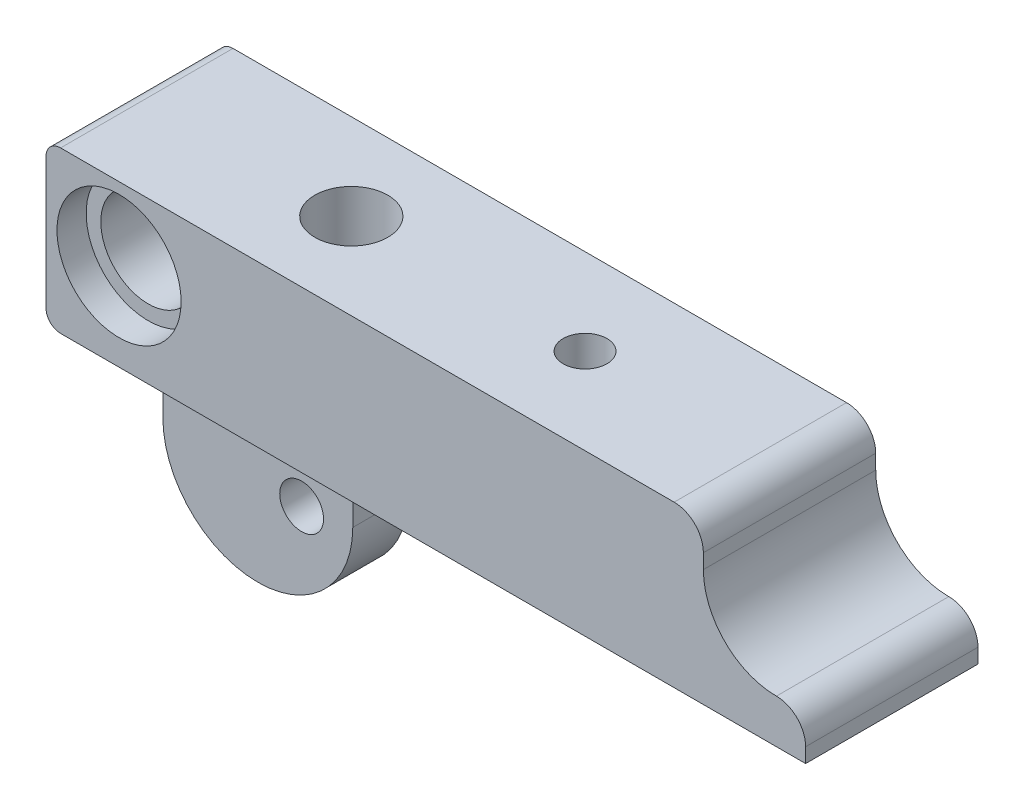
SolidWorks part; units mm, degrees
ref_plane "前视基准面" through (0, 0, 0) normal (0, 0, 1) x (1, 0, 0)
ref_plane "上视基准面" through (0, 0, 0) normal (0, 1, 0) x (1, 0, 0)
ref_plane "右视基准面" through (0, 0, 0) normal (1, 0, 0) x (0, 0, -1)
sketch "草图1" plane through (0, 0, 0) normal (0, 0, 1) x (1, 0, 0)
  line L0 (35.7215, -3) -> (42.7215, -3)
  line L1 (-9.2785, 8) -> (35.7215, 8)
  line L2 (-9.2785, 8) -> (-9.2785, -3)
  line L3 (3.7215, -3) -> (35.7215, -3)
  line L4 (35.7215, 8) -> (35.7215, 0)
  line L5 (-9.2785, 8) -> (35.7215, -3) construction
  line L6 (13.2215, 2.5) -> (35.7215, 8) construction
  line L7 (42.7215, -3) -> (42.7215, 0)
  line L8 (42.7215, 0) -> (35.7215, 0)
  line L9 (-9.2785, -3) -> (-9.2785, -12.5)
  line L11 (3.7215, -12.5) -> (3.7215, -3)
  arc A0 (-9.2785, -12.5) -> (3.7215, -12.5) centre (-2.7785, -12.5) ccw
  circle A1 centre (0.2215, -13) radius 1.5
  point P4 (13.2215, 2.5)
  dimension "D7" = 3
  dimension "D1" = 45
  dimension "D2" = 11
  dimension "D3" = 3
  dimension "D4" = 52
  dimension "D5" = 13
  dimension "D6" = 9.5
  dimension "D8" = 3.5
  dimension "D9" = 10
extrude "凸台-拉伸1" add sketch "草图1" along normal blind 3.8
sketch "草图2" plane through (0, 0, 3.8) normal (0, 0, 1) x (1, 0, 0)
  line L0 (3.7215, -3) -> (-9.2785, -3)
  line L7 (-9.2785, 8) -> (-9.2785, -12.5)
  line L8 (3.7215, -12.5) -> (3.7215, -3)
  line L9 (3.7215, -3) -> (42.7215, -3)
  line L10 (42.7215, -3) -> (42.7215, 0)
  line L11 (42.7215, 0) -> (35.7215, 0)
  line L12 (35.7215, 0) -> (35.7215, 8)
  line L13 (35.7215, 8) -> (-9.2785, 8)
  line L14 (-9.2785, 8) -> (-9.2785, -3)
  line L16 (3.7215, -3) -> (42.7215, -3)
  line L17 (42.7215, -3) -> (42.7215, 0)
  line L18 (42.7215, 0) -> (35.7215, 0)
  line L19 (35.7215, 0) -> (35.7215, 8)
  line L20 (35.7215, 8) -> (-9.2785, 8)
  arc A1 (-9.2785, -12.5) -> (3.7215, -12.5) centre (-2.7785, -12.5) ccw
  dimension "D1" = 0
extrude "凸台-拉伸2" add sketch "草图2" along normal blind 8
sketch "草图3" plane through (0, 0, 11.8) normal (0, 0, 1) x (1, 0, 0)
  line L0 (35.7215, 8) -> (-9.2785, 8) construction
  line L2 (-9.2785, 8) -> (-9.2785, -3) construction
  circle A0 centre (-4.2785, 3) radius 3.25
  point P6 (-9.2785, 1.2956)
  point P7 (-3.6397, 8.3733)
  point P8 (0, 0)
  dimension "D1" = 6.5
  dimension "D2" = 5
  dimension "D3" = 5
extrude "切除-拉伸1" cut sketch "草图3" against normal through all
sketch "草图4" plane through (0, 0, 11.8) normal (0, 0, 1) x (1, 0, 0)
  circle A0 centre (-4.2785, 3) radius 4.25
  dimension "D1" = 8.5
extrude "切除-拉伸2" cut sketch "草图4" against normal blind 2
fillet "圆角2" radius 1 2 edges at (-9.2785, -3, 7.8) (-9.2785, 8, 5.9)
fillet "圆角3" radius 2 1 edges at (35.7215, 8, 5.9)
fillet "圆角4" radius 5 1 edges at (35.7215, 0, 5.9)
fillet "圆角5" radius 2 1 edges at (42.7215, 0, 5.9)
sketch "草图5" plane through (0, 8, 0) normal (0, 1, 0) x (1, 0, 0)
  line L0 (-8.2785, -5.9) -> (33.7215, -5.9) construction
  line L1 (-8.2785, 0) -> (-8.2785, -11.8) construction
  line L2 (33.7215, -11.8) -> (33.7215, 0) construction
  line L3 (-9.2785, -11.8) -> (-9.2785, 0) construction
  circle A0 centre (5.7215, -5.9) radius 2.5
  circle A1 centre (21.7215, -5.9) radius 1.5
  dimension "D3" = 5
  dimension "D4" = 3
  dimension "D1" = 15
  dimension "D2" = 16
extrude "切除-拉伸3" cut sketch "草图5" against normal through all
